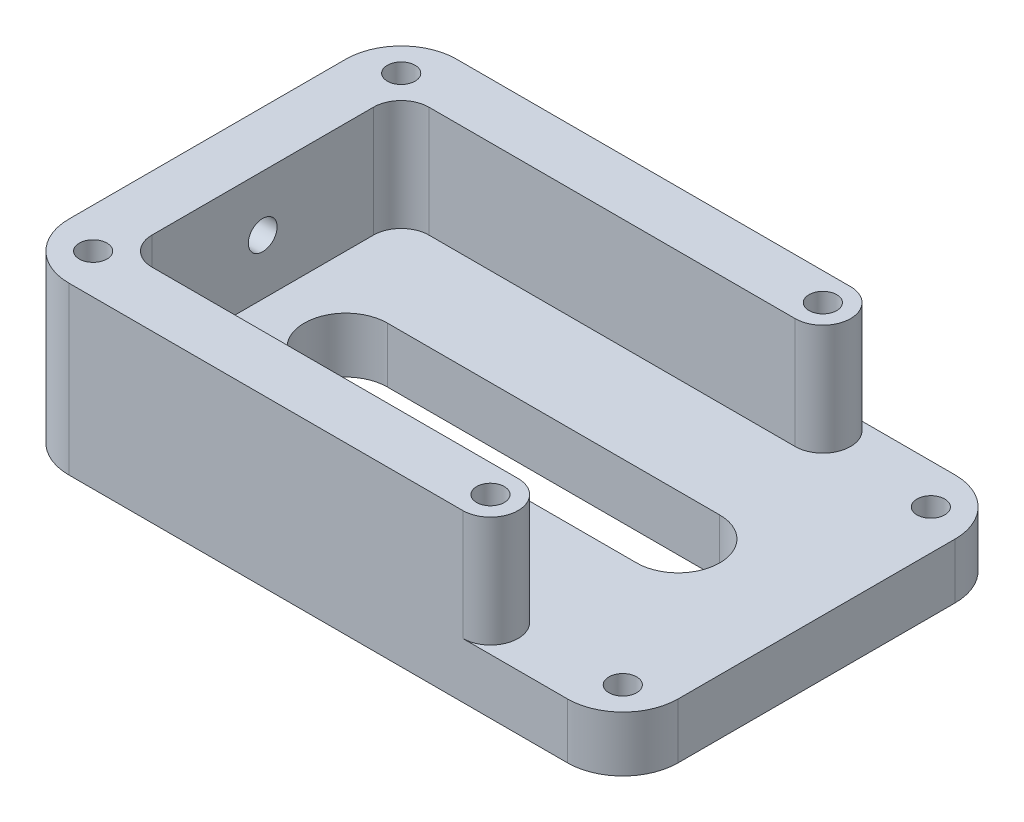
SolidWorks part; units mm, degrees
ref_plane "Front Plane" through (0, 0, 0) normal (0, 0, 1) x (1, 0, 0)
ref_plane "Top Plane" through (0, 0, 0) normal (0, 1, 0) x (1, 0, 0)
ref_plane "Right Plane" through (0, 0, 0) normal (1, 0, 0) x (0, 0, -1)
sketch "Sketch1" plane through (0, 0, 0) normal (0, 1, 0) x (1, 0, 0)
  line L1 (-45, 35) -> (26.1138, 35)
  line L2 (-55, 25) -> (-55, -25)
  line L3 (-45, -35) -> (26.7374, -35)
  line L4 (55, 25) -> (55, -25)
  line L5 (-55, 35) -> (55, -35) construction
  line L6 (-55, -35) -> (55, 35) construction
  line L10 (-45, 20) -> (-45, -20)
  line L11 (-40, -25) -> (40, -25)
  line L12 (45, 20) -> (45, -20)
  line L13 (-40, 25) -> (40, 25)
  line L14 (-55, 0) -> (55, 0) construction
  line L15 (-45, -25) -> (45, -25) construction
  line L16 (-45, 25) -> (-45, -25) construction
  line L17 (45, 25) -> (45, -25) construction
  line L18 (-45, 25) -> (45, 25) construction
  line L19 (43.5355, 23.5355) -> (52.0711, 32.0711) construction
  line L20 (-30, 0) -> (30, 0) construction
  line L21 (-45, -35) -> (45, -35) construction
  line L22 (-45, 35) -> (45, 35) construction
  line L23 (26.1138, 35) -> (45, 35)
  line L24 (45, -35) -> (26.7374, -35)
  line L25 (-30, 7.5) -> (30, 7.5)
  line L26 (-30, -7.5) -> (30, -7.5)
  circle A0 centre (27.6447, 0) radius 8 construction
  arc A1 (-55, -25) -> (-45, -35) centre (-45, -25) ccw
  arc A2 (45, -35) -> (55, -25) centre (45, -25) ccw
  arc A3 (45, 35) -> (55, 25) centre (45, 25) cw
  arc A4 (-45, 35) -> (-55, 25) centre (-45, 25) ccw
  arc A17 (-40, -25) -> (-45, -20) centre (-40, -20) cw
  arc A18 (-45, -25) -> (-45, -25) centre (-45, -25) ccw construction
  arc A19 (45, -20) -> (40, -25) centre (40, -20) cw
  arc A20 (45, -25) -> (45, -25) centre (45, -25) ccw construction
  arc A21 (40, 25) -> (45, 20) centre (40, 20) cw
  arc A22 (45, 25) -> (45, 25) centre (45, 25) cw construction
  arc A23 (-40, 25) -> (-45, 20) centre (-40, 20) ccw
  arc A24 (-45, 25) -> (-45, 25) centre (-45, 25) ccw construction
  circle A25 centre (26.1138, 30) radius 5
  circle A26 centre (26.1138, -30) radius 5
  circle A27 centre (47.8033, 27.8033) radius 2.5
  circle A28 centre (47.8033, -27.8033) radius 2.5
  arc A29 (-30, 7.5) -> (-30, -7.5) centre (-30, 0) ccw
  arc A30 (30, -7.5) -> (30, 7.5) centre (30, 0) ccw
  point P0 (0, 0)
  point P60 (0, 0)
  point P65 (0, 0)
  point P66 (0, 0)
  point P67 (-29.5474, 0)
  point P68 (0, 0)
  point P69 (-37.5, 0)
  point P70 (37.5, 0)
  dimension "D1" = 10
  dimension "D3" = 5
  dimension "D4" = 110
  dimension "D5" = 70
  dimension "D6" = 60
  dimension "D7" = 17.5
  dimension "D8" = 17.5
  dimension "D2" = 10
extrude "Boss-Extrude1" add sketch "Sketch1" along normal blind 10 contours L13 A23 L10 A17 L11 A19 L12 A21 | L3 A26 L11 A17 L10 A23 L13 A25 L1 A4 L2 A1 | L11 A26 L3 L24 A2 L4 A3 L23 A25 L13 A21 L12 A19 | A25 | A26 A4 region at (-9.4431, 0, -33.9286) region at (45.8562, 0, 0) region at (26.1138, 0, -30) region at (33.0569, 0, -23.9704) region at (26.1138, 0, 30)
extrude "Boss-Extrude2" add sketch "Sketch1<6>" along normal blind 30 contours L3 A26 L11 A17 L10 A23 L13 A25 L1 A4 L2 A1 | A25 | A26 region at (-9.4431, 0, -33.9286) region at (26.1138, 0, -30) region at (26.1138, 0, 30)
sketch "Sketch1<6>" plane through (0, 0, 0) normal (0, 1, 0) x (1, 0, 0) same geometry as "Sketch1"
sketch "Sketch3" plane through (0, 30, 0) normal (0, 1, 0) x (1, 0, 0)
  line L0 (-43.5355, 23.5355) -> (-52.0711, 32.0711) construction
  line L1 (-55, 0) -> (55, 0) construction
  line L2 (-55, 25) -> (-55, -25) construction
  line L3 (55, 25) -> (55, -25) construction
  line L4 (26.1138, 35) -> (26.1138, 25) construction
  line L5 (26.1138, 35) -> (45, 35) construction
  arc A0 (-40, 25) -> (-45, 20) centre (-40, 20) ccw construction
  arc A1 (-45, 35) -> (-55, 25) centre (-45, 25) ccw construction
  circle A2 centre (-47.8033, 27.8033) radius 2.5
  circle A3 centre (-47.8033, -27.8033) radius 2.5
  circle A4 centre (26.1138, 30) radius 2.5
  circle A5 centre (26.1138, -30) radius 2.5
extrude "Cut-Extrude1" cut sketch "Sketch3" against normal blind 30
sketch "Sketch6" plane through (-45, 0, 0) normal (1, 0, 0) x (0, 0, -1)
  line L0 (0, 30) -> (0, 10) construction
  line L1 (20, 30) -> (-20, 30) construction
  line L2 (-20, 10) -> (20, 10) construction
  circle A0 centre (0, 20) radius 2.6
extrude "Cut-Extrude3" cut sketch "Sketch6" against normal blind 11
